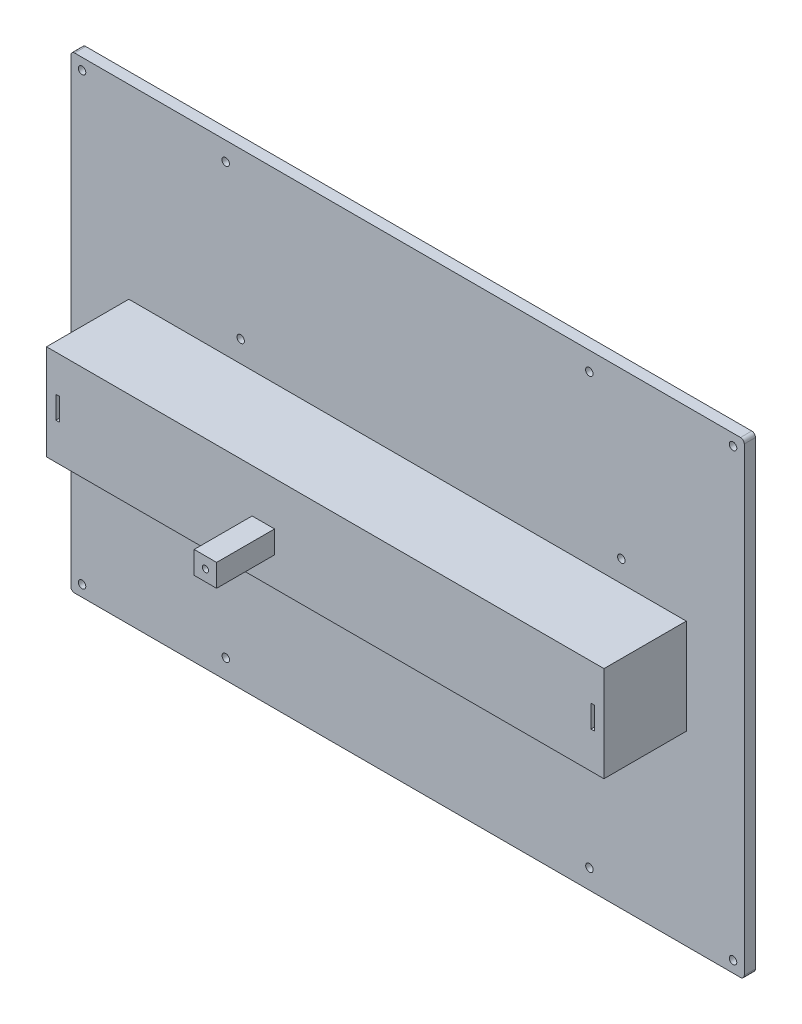
SolidWorks part; units mm, degrees
ref_plane "前视基准面" through (0, 0, 0) normal (0, 0, 1) x (1, 0, 0)
ref_plane "上视基准面" through (0, 0, 0) normal (0, 1, 0) x (1, 0, 0)
ref_plane "右视基准面" through (0, 0, 0) normal (1, 0, 0) x (0, 0, -1)
sketch "草图1" plane through (0, 0, 0) normal (0, 0, 1) x (1, 0, 0)
  line L1 (-90, 62.5) -> (90, 62.5)
  line L2 (-90, 62.5) -> (-90, -62.5)
  line L3 (-90, -62.5) -> (90, -62.5)
  line L4 (90, 62.5) -> (90, -62.5)
  line L5 (-90, 62.5) -> (90, -62.5) construction
  line L6 (-90, -62.5) -> (90, 62.5) construction
  point P0 (0, 0)
  dimension "D1" = 125
  dimension "D2" = 180
extrude "凸台-拉伸1" add sketch "草图1" along normal blind 3
sketch "草图7" plane through (0, 0, 0) normal (0, 0, -1) x (-1, 0, 0)
  line L1 (-72, 10.25) -> (72, 10.25)
  line L2 (-72, 10.25) -> (-72, -10.25)
  line L3 (-72, -10.25) -> (72, -10.25)
  line L4 (72, 10.25) -> (72, -10.25)
  line L5 (0, 0) -> (72.729, 0) construction
  line L8 (0, 0) -> (0, -50.9103) construction
  dimension "D1" = 20.5
  dimension "D2" = 144
extrude "电池位切除-拉伸3" cut sketch "草图7" against normal up to next
sketch "草图8" plane through (0, 0, 3) normal (0, 0, 1) x (1, 0, 0)
  line L12 (72, 10.25) -> (72, -10.25) construction
  line L13 (-74.5, 12.75) -> (74.5, 12.75)
  line L14 (-74.5, 12.75) -> (-74.5, -12.75)
  line L15 (-74.5, -12.75) -> (74.5, -12.75)
  line L16 (74.5, 12.75) -> (74.5, -12.75)
  line L17 (-72, -10.25) -> (-72, 10.25) construction
  line L18 (-72, 10.25) -> (72, 10.25) construction
  line L19 (72, -10.25) -> (-72, -10.25) construction
  line L20 (-72, 10.25) -> (72, 10.25)
  line L21 (72, -10.25) -> (-72, -10.25)
  line L22 (72, 10.25) -> (72, -10.25)
  line L23 (-72, -10.25) -> (-72, 10.25) construction
  line L24 (-72, -10.25) -> (-72, 10.25)
  dimension "D1" = 2.5
  dimension "D2" = 2.5
  dimension "D3" = 2.5
  dimension "D4" = 2.5
extrude "凸台-拉伸2" add sketch "草图8" along normal blind 22
sketch "草图9" plane through (0, 0, 25) normal (0, 0, 1) x (1, 0, 0)
  line L0 (74.5, 12.75) -> (-74.5, 12.75) construction
  line L5 (74.5, 12.75) -> (-74.5, 12.75)
  line L6 (-74.5, -12.75) -> (74.5, -12.75) construction
  line L7 (-74.5, -12.75) -> (74.5, -12.75)
  line L8 (74.5, -12.75) -> (74.5, 12.75) construction
  line L9 (74.5, -12.75) -> (74.5, 12.75)
  line L10 (-74.5, 12.75) -> (-74.5, -12.75) construction
  line L11 (-74.5, 12.75) -> (-74.5, -12.75)
extrude "凸台-拉伸3" add sketch "草图9" against normal blind 2.5
sketch "草图4" plane through (0, 0, 0) normal (0, 0, -1) x (-1, 0, 0)
  line L0 (72, -10.25) -> (72, 10.25) construction
  line L5 (72, 0) -> (84.6307, 0) construction
  line L10 (83.2374, -53.4277) -> (79.3374, -53.4277) construction
  line L11 (83.2374, -49.6277) -> (83.2374, -53.4277) construction
  line L12 (79.3374, -49.6277) -> (83.2374, -49.6277) construction
  line L29 (72, -4) -> (76, -4)
  line L30 (76, -4) -> (76, 4)
  line L31 (76, 4) -> (72, 4)
  line L32 (72, 4) -> (72, -4)
  dimension "D1" = 8
  dimension "D2" = 4
extrude "切除-拉伸2" cut sketch "草图4" against normal blind 2 from offset 1.5 offset against normal yes
sketch "草图10" plane through (0, 0, 25) normal (0, 0, 1) x (1, 0, 0)
  line L0 (-16.5366, -1.9347) -> (8.5541, -1.9347) construction
  line L2 (-19.5366, 1.0653) -> (-19.5366, -4.9347)
  line L4 (-13.5366, 1.0653) -> (-13.5366, -4.9347)
  line L5 (-16.5366, -1.9347) -> (-16.5366, 4.0653) construction
  line L6 (0, 0) -> (60.8594, 0) construction
  line L7 (0, 0) -> (0, 60.5) construction
  line L8 (75, 60.5) -> (-75, 60.5) construction
  line L9 (-19.5366, 1.0653) -> (-13.5366, 1.0653)
  line L10 (-19.5366, -4.9347) -> (-13.5366, -4.9347)
  circle A0 centre (-16.5366, -1.9347) radius 0.825
  dimension "D2" = 1.65
  dimension "D1" = 6
extrude "凸台-拉伸4" add sketch "草图10" along normal up to surface (15.5 mm away)
sketch "草图11" plane through (0, 0, 0) normal (0, 0, -1) x (-1, 0, 0)
  circle A0 centre (-48.6147, -57.3) radius 1 construction
  circle A1 centre (-44.6, -18.3) radius 1 construction
  circle A2 centre (57.15, -18.3) radius 1 construction
  circle A3 centre (48.5747, -57.3) radius 1 construction
  circle A4 centre (87, 59.5) radius 1
  circle A5 centre (48.6147, 57.5) radius 1 construction
  circle A6 centre (-57.15, 18.5) radius 1 construction
  circle A7 centre (-48.5747, 57.5) radius 1 construction
  circle A8 centre (-48.6147, -57.3) radius 1
  circle A9 centre (-44.6, -18.3) radius 1
  circle A10 centre (57.15, -18.3) radius 1
  circle A11 centre (48.5747, -57.3) radius 1
  circle A13 centre (48.6147, 57.5) radius 1
  circle A14 centre (-57.15, 18.5) radius 1
  circle A15 centre (-48.5747, 57.5) radius 1
  circle A16 centre (44.6, 18.5) radius 1 construction
  circle A17 centre (44.6, 18.5) radius 1
  circle A18 centre (87, -59.5) radius 1
  circle A19 centre (-87, -59.5) radius 1
  circle A20 centre (-87, 59.5) radius 1
  dimension "D1" = 2
  dimension "D2" = 2
  dimension "D3" = 2
  dimension "D4" = 2
extrude "固定螺丝切除-拉伸3" cut sketch "草图11" against normal up to next
sketch "草图12" plane through (0, 0, 0) normal (0, 0, -1) x (-1, 0, 0)
  circle A0 centre (-48.5747, 57.5) radius 2
  circle A1 centre (-57.15, 18.5) radius 2
  circle A2 centre (-44.6, -18.3) radius 2
  circle A3 centre (-48.6147, -57.3) radius 2
  circle A4 centre (48.5747, -57.3) radius 2
  circle A5 centre (57.15, -18.3) radius 2
  circle A7 centre (-87, 59.5) radius 2
  circle A8 centre (48.6147, 57.5) radius 2
  circle A9 centre (44.6, 18.5) radius 2
  circle A10 centre (-87, -59.5) radius 2
  circle A11 centre (87, -59.5) radius 2
  circle A12 centre (87, 59.5) radius 2
  dimension "D1" = 4
  dimension "D2" = 4
  dimension "D3" = 4
  dimension "D4" = 4
  dimension "D5" = 4
extrude "固定螺丝凹陷切除-拉伸4" cut sketch "草图12" against normal blind 1.2
fillet "圆角1" radius 1 4 edges at (90, -62.5, 1.5) (-90, -62.5, 1.5) (-90, 62.5, 1.5) (90, 62.5, 1.5)
sketch "草图13" plane through (0, 0, 25) normal (0, 0, 1) x (1, 0, 0)
  line L0 (72, 10.25) -> (72, -10.25) construction
  line L1 (72, 3) -> (71, 3)
  line L2 (72, 3) -> (72, -3)
  line L3 (72, -3) -> (71, -3)
  line L4 (71, 3) -> (71, -3)
  line L5 (-72, -10.25) -> (-72, 10.25) construction
  line L6 (-71, 3) -> (-72, 3)
  line L7 (-71, 3) -> (-71, -3)
  line L8 (-71, -3) -> (-72, -3)
  line L9 (-72, 3) -> (-72, -3)
  line L10 (72, 0) -> (59.7453, 0) construction
  dimension "D1" = 1
  dimension "D2" = 6
  dimension "D3" = 1
  dimension "D4" = 6
extrude "切除-拉伸3" cut sketch "草图13" against normal up to next
sketch "草图14" plane through (0, 0, 22.5) normal (0, 0, -1) x (-1, 0, 0)
  line L0 (72, 10.25) -> (-72, 10.25) construction
  line L1 (-71, 10.25) -> (-69, 10.25)
  line L2 (-71, 10.25) -> (-71, 5.25)
  line L3 (-71, 5.25) -> (-69, 5.25)
  line L4 (-69, 10.25) -> (-69, 5.25)
  line L5 (-72, 0) -> (-60.8543, 0) construction
  line L6 (-72, 10.25) -> (-72, -10.25) construction
  line L7 (72, 0) -> (63.4917, 0) construction
  line L8 (69, 10.25) -> (71, 10.25)
  line L9 (69, 10.25) -> (69, 5.75)
  line L10 (69, 5.75) -> (71, 5.75)
  line L11 (71, 10.25) -> (71, 5.75)
  line L12 (72, -10.25) -> (72, 10.25) construction
  line L13 (71, -10.25) -> (71, -5.75)
  line L14 (69, -5.75) -> (71, -5.75)
  line L15 (69, -10.25) -> (69, -5.75)
  line L16 (69, -10.25) -> (71, -10.25)
  line L17 (-69, -10.25) -> (-69, -5.25)
  line L18 (-71, -5.25) -> (-69, -5.25)
  line L19 (-71, -10.25) -> (-71, -5.25)
  line L20 (-71, -10.25) -> (-69, -10.25)
  dimension "D1" = 1
  dimension "D2" = 2
  dimension "D3" = 4.5
  dimension "D4" = 1
  dimension "D5" = 2
  dimension "D6" = 5
extrude "凸台-拉伸5" add sketch "草图14" along normal blind 16
